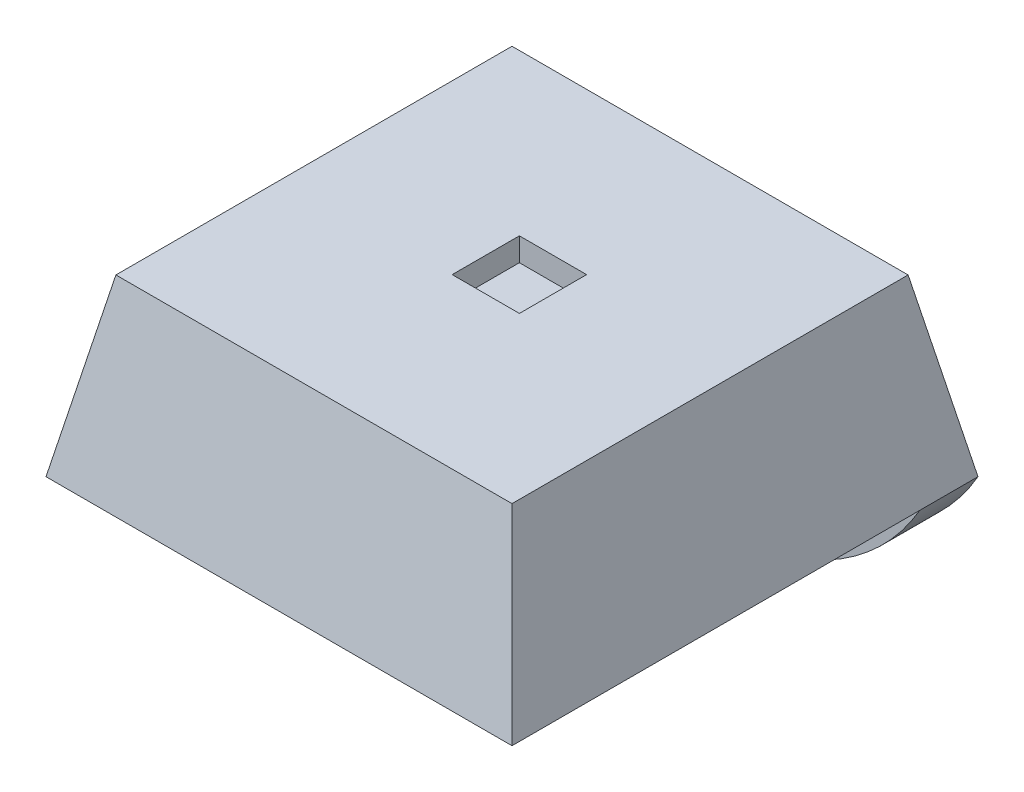
SolidWorks part; units mm, degrees
ref_plane "Front Plane" through (0, 0, 0) normal (0, 0, 1) x (1, 0, 0)
ref_plane "Top Plane" through (0, 0, 0) normal (0, 1, 0) x (1, 0, 0)
ref_plane "Right Plane" through (0, 0, 0) normal (1, 0, 0) x (0, 0, -1)
sketch "Sketch1" plane through (0, 0, 0) normal (0, 1, 0) x (1, 0, 0)
  line L1 (0, 0) -> (8, 0)
  line L2 (0, 0) -> (0, 8)
  line L3 (0, 8) -> (8, 8)
  line L4 (8, 0) -> (8, 8)
  dimension "D1" = 8
  dimension "D2" = 8
extrude "Boss-Extrude1" add sketch "Sketch1" along normal blind 3
sketch "Sketch2" plane through (0, 0, 0) normal (0, 0, 1) x (1, 0, 0)
  line L0 (0, 0) -> (0.6, 3)
  line L1 (0, 3) -> (8, 3) construction
  line L2 (0.6, 3) -> (0, 3)
  line L3 (0, 3) -> (0, 0)
  line L4 (8, 0) -> (7.4, 3)
  line L5 (7.4, 3) -> (8, 3)
  line L6 (8, 3) -> (8, 0)
  dimension "D1" = 0.6
  dimension "D2" = 0.6
extrude "Cut-Extrude1" cut sketch "Sketch2" against normal through all both and the other way through all
sketch "Sketch3" plane through (0, 0, 0) normal (1, 0, 0) x (0, 0, -1)
  line L0 (0, 0) -> (0.6, 3)
  line L1 (8, 3) -> (0, 3) construction
  line L2 (0.6, 3) -> (0, 3)
  line L3 (0, 3) -> (0, 0)
  line L4 (8, 3) -> (7.4, 3)
  line L5 (7.4, 3) -> (8, 0)
  line L6 (8, 3) -> (8, 0)
  dimension "D1" = 0.6
  dimension "D2" = 0.6
extrude "Cut-Extrude2" cut sketch "Sketch3" along normal blind 11
sketch "Sketch4" plane through (0, 0, 0) normal (0, -1, 0) x (1, 0, 0)
  line L0 (8, 0) -> (8, -8) construction
  line L3 (0, 0) -> (8, 0) construction
  circle A0 centre (4, -3.75) radius 1.8
  dimension "D1" = 3.6
  dimension "D2" = 4
  dimension "D3" = 3.75
extrude "Cut-Extrude3" cut sketch "Sketch4" against normal blind 0.8
sketch "Sketch5" plane through (0, 0, 0) normal (0, -1, 0) x (1, 0, 0)
  line L0 (8, 0) -> (8, -8) construction
  line L1 (0, -8) -> (8, -8)
  line L2 (0, -8) -> (0, -7)
  line L3 (0, -7) -> (8, -7)
  line L4 (8, -8) -> (8, -7)
  dimension "D1" = 1
extrude "Boss-Extrude2" add sketch "Sketch5" along normal blind 2
fillet "Fillet1" radius 4 2 edges at (8, -2, -7.5) (0, -2, -7.5)
sketch "Sketch6" plane through (0, 3, 0) normal (0, 1, 0) x (1, 0, 0)
  text T0 "." font "Arial" height 6
extrude "Cut-Extrude4" cut sketch "Sketch6" against normal blind 0.4
